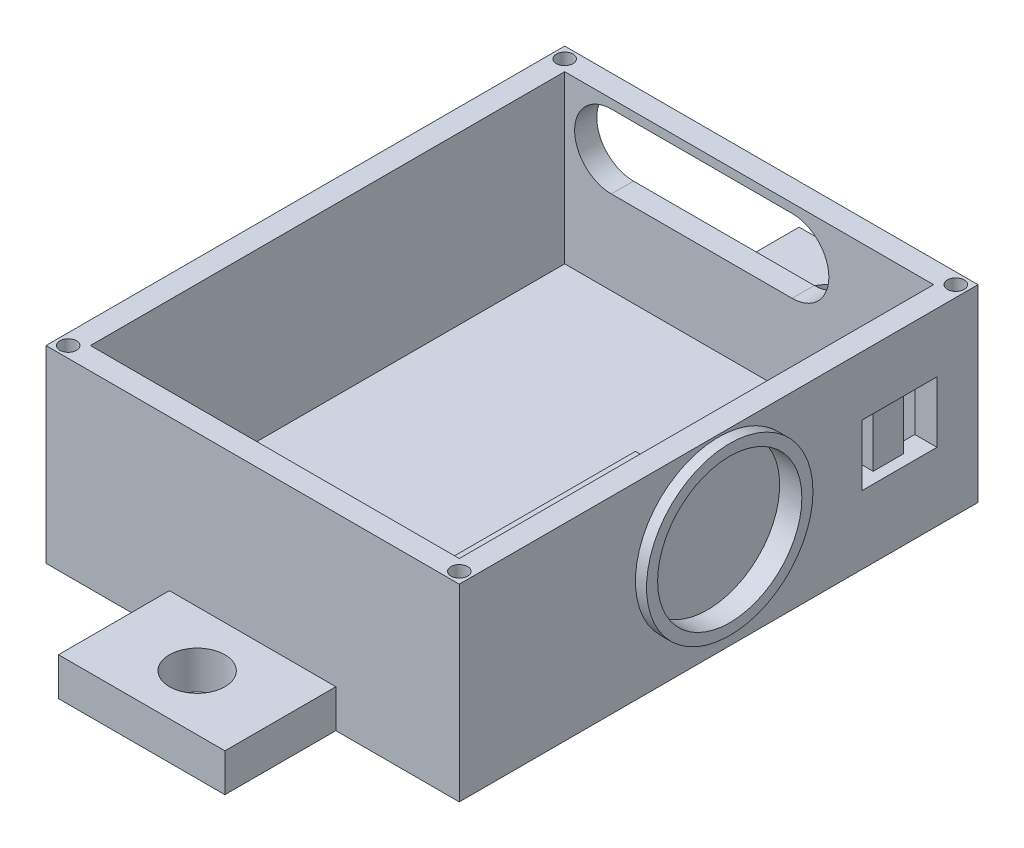
SolidWorks part; units mm, degrees
ref_plane "Front Plane" through (0, 0, 0) normal (0, 0, 1) x (1, 0, 0)
ref_plane "Top Plane" through (0, 0, 0) normal (0, 1, 0) x (1, 0, 0)
ref_plane "Right Plane" through (0, 0, 0) normal (1, 0, 0) x (0, 0, -1)
sketch "Sketch2" plane through (0, 0, 0) normal (0, 1, 0) x (1, 0, 0)
  line L1 (-37.25, 46.75) -> (37.25, 46.75)
  line L2 (-37.25, 46.75) -> (-37.25, -46.75)
  line L3 (-37.25, -46.75) -> (37.25, -46.75)
  line L4 (37.25, 46.75) -> (37.25, -46.75)
  line L5 (-37.25, 46.75) -> (37.25, -46.75) construction
  line L6 (-37.25, -46.75) -> (37.25, 46.75) construction
  point P0 (0, 0)
  dimension "D1" = 74.5
  dimension "D2" = 93.5
extrude "Boss-Extrude1" add sketch "Sketch2" along normal blind 34
shell "Shell1" thickness 4 removed face at (0, 34, 0)
ref_plane "Plane1" through (37.25, 34, 46.75) normal (0, 0, -1) x (-1, 0, 0)
sketch "Sketch4" plane through (37.25, 0, 0) normal (1, 0, 0) x (0, 0, -1)
  line L0 (-46.75, 34) -> (46.75, 34) construction
  circle A0 centre (0, 18.6) radius 15
  dimension "D1" = 30
  dimension "D2" = 15.4
extrude "Boss-Extrude2" add sketch "Sketch4" along normal blind 2
shell "Shell2" thickness 2 removed face at (39.25, 18.6, -15)
sketch "Sketch5" plane through (33.25, 0, 0) normal (-1, 0, 0) x (0, 0, 1)
  line L1 (0, 23.8569) -> (33, 23.8569)
  line L2 (0, 23.8569) -> (0, 6.8569)
  line L3 (0, 6.8569) -> (33, 6.8569)
  line L4 (33, 23.8569) -> (33, 6.8569)
  dimension "D1" = 33
  dimension "D2" = 17
extrude "Boss-Extrude3" add sketch "Sketch5" along normal blind 11
shell "Shell3" thickness 2 removed face at (27.75, 23.8569, 16.5)
ref_plane "Plane2" through (22.25, 6.8569, 33) normal (0, 1, 0) x (1, 0, 0)
sketch "Sketch8" plane through (0, 0, 31) normal (0, 0, -1) x (-1, 0, 0)
  line L0 (-24.25, 8.8569) -> (-35.25, 8.8569) construction
  line L1 (-24.25, 23.8569) -> (-28.75, 23.8569)
  line L2 (-24.25, 23.8569) -> (-24.25, 8.8569)
  line L3 (-24.25, 8.8569) -> (-28.75, 8.8569)
  line L4 (-28.75, 23.8569) -> (-28.75, 8.8569)
extrude "Cut-Extrude1" cut sketch "Sketch8" against normal blind 7
sketch "Sketch9" plane through (0, 34, 0) normal (0, 1, 0) x (1, 0, 0)
  line L0 (-33.25, -42.75) -> (-37.25, -46.75) construction
  line L1 (33.25, -42.75) -> (37.25, -46.75) construction
  line L2 (33.25, 42.75) -> (37.25, 46.75) construction
  line L3 (-37.25, 46.75) -> (-33.25, 42.75) construction
  circle A0 centre (-35.25, -44.75) radius 1.5
  circle A1 centre (35.25, -44.75) radius 1.5
  circle A2 centre (35.25, 44.75) radius 1.5
  circle A3 centre (-35.25, 44.75) radius 1.5
  dimension "D1" = 3
  dimension "D2" = 3
  dimension "D3" = 3
  dimension "D4" = 3
extrude "Cut-Extrude3" cut sketch "Sketch9" against normal blind 7
sketch "Sketch10" plane through (37.25, 0, 0) normal (1, 0, 0) x (0, 0, -1)
  line L1 (25.8545, 23.3116) -> (39.3545, 23.3116)
  line L2 (25.8545, 23.3116) -> (25.8545, 12.3116)
  line L3 (25.8545, 12.3116) -> (39.3545, 12.3116)
  line L4 (39.3545, 23.3116) -> (39.3545, 12.3116)
  line L5 (25.8545, 23.3116) -> (39.3545, 12.3116) construction
  line L6 (25.8545, 12.3116) -> (39.3545, 23.3116) construction
  point P0 (32.6045, 17.8116)
  dimension "D1" = 11
  dimension "D2" = 13.5
extrude "Cut-Extrude5" cut sketch "Sketch10" against normal blind 2
sketch "Sketch11" plane through (35.25, 0, 0) normal (1, 0, 0) x (0, 0, -1)
  line L0 (25.8545, 12.3116) -> (39.3545, 12.3116) construction
  line L1 (25.8545, 23.3116) -> (29.8545, 23.3116)
  line L2 (25.8545, 23.3116) -> (25.8545, 12.3116)
  line L3 (25.8545, 12.3116) -> (29.8545, 12.3116)
  line L4 (29.8545, 23.3116) -> (29.8545, 12.3116)
  line L5 (25.8545, 12.3116) -> (39.3545, 12.3116) construction
  line L6 (39.3545, 23.3116) -> (35.3545, 23.3116)
  line L7 (39.3545, 23.3116) -> (39.3545, 12.3116)
  line L8 (39.3545, 12.3116) -> (35.3545, 12.3116)
  line L9 (35.3545, 23.3116) -> (35.3545, 12.3116)
  dimension "D1" = 4
  dimension "D2" = 4
extrude "Cut-Extrude6" cut sketch "Sketch11" against normal blind 12
sketch "Sketch12" plane through (0, 0, -46.75) normal (0, 0, -1) x (-1, 0, 0)
  line L0 (-7.7421, 25.7421) -> (24.8421, 25.7421) construction
  line L1 (-7.7421, 32.3679) -> (24.8421, 32.3679)
  line L2 (-7.7421, 19.1162) -> (24.8421, 19.1162)
  line L3 (37.25, 34) -> (37.25, 0) construction
  arc A0 (-7.7421, 32.3679) -> (-7.7421, 19.1162) centre (-7.7421, 25.7421) ccw
  arc A1 (24.8421, 19.1162) -> (24.8421, 32.3679) centre (24.8421, 25.7421) ccw
  point P2 (8.55, 25.7421)
  point P9 (-7.7421, 30.3679)
  dimension "D1" = 28.7
extrude "Cut-Extrude7" cut sketch "Sketch12" against normal blind 10
sketch "Sketch13" plane through (0, 0, -46.75) normal (0, 0, -1) x (-1, 0, 0)
  line L0 (-15, 0) -> (-15, 34) construction
  line L1 (-37.25, 0) -> (37.25, 0) construction
  line L2 (-37.25, 34) -> (37.25, 34) construction
  line L3 (15, 0) -> (15, 34) construction
  line L4 (-17.575, 6.8569) -> (-26.925, 6.8569) construction
  line L5 (-15, 0) -> (15, 0)
  line L6 (-15, 0) -> (-15, 6.8569)
  line L7 (-15, 6.8569) -> (15, 6.8569)
  line L8 (15, 0) -> (15, 6.8569)
  line L9 (-33.25, 4) -> (33.25, 4) construction
  dimension "D1" = 15
  dimension "D2" = 15
  dimension "D3" = 6.8569
extrude "Boss-Extrude6" add sketch "Sketch13" along normal blind 20
sketch "Sketch19" plane through (0, 0, 46.75) normal (0, 0, 1) x (1, 0, 0)
  line L0 (-15, 34) -> (-15, 0) construction
  line L1 (-37.25, 34) -> (37.25, 34) construction
  line L2 (-37.25, 0) -> (37.25, 0) construction
  line L3 (15, 34) -> (15, 0) construction
  line L5 (-15, 0) -> (15, 0)
  line L6 (-15, 0) -> (-15, 6.86)
  line L7 (-15, 6.86) -> (15, 6.86)
  line L8 (15, 0) -> (15, 6.86)
  dimension "D1" = 15
  dimension "D2" = 15
  dimension "D3" = 6.86
extrude "Boss-Extrude7" add sketch "Sketch19" along normal blind 20
sketch "Sketch20" plane through (0, 6.8569, 0) normal (0, 1, 0) x (1, 0, 0)
  circle A0 centre (0, 56.75) radius 5
  dimension "D1" = 10
extrude "Cut-Extrude8" cut sketch "Sketch20" against normal blind 20
sketch "Sketch21" plane through (0, 6.86, 0) normal (0, 1, 0) x (1, 0, 0)
  circle A0 centre (0, -56.75) radius 5
  dimension "D1" = 10
extrude "Cut-Extrude9" cut sketch "Sketch21" against normal blind 20
